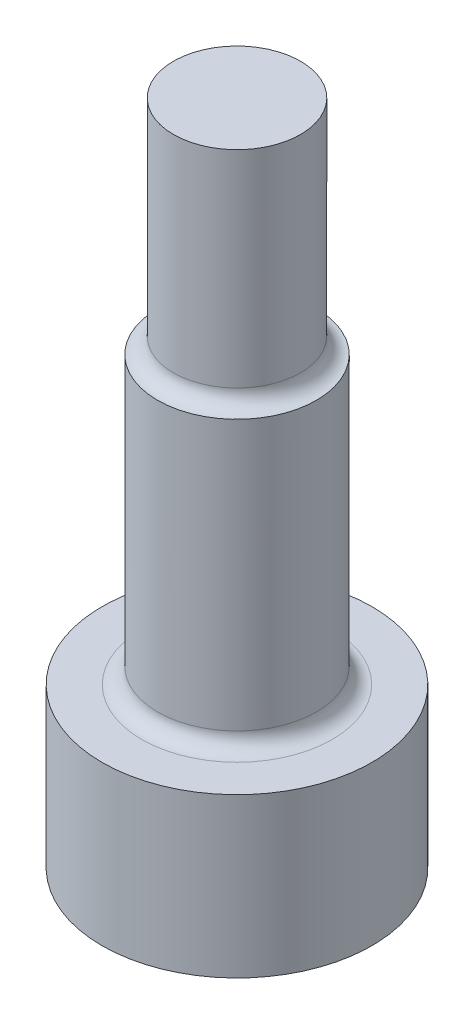
SolidWorks part; units mm, degrees
material "Chrome Stainless Steel"
ref_plane "Front Plane" through (0, 0, 0) normal (0, 0, 1) x (1, 0, 0)
ref_plane "Top Plane" through (0, 0, 0) normal (0, 1, 0) x (1, 0, 0)
ref_plane "Right Plane" through (0, 0, 0) normal (1, 0, 0) x (0, 0, -1)
sketch "Sketch1" plane through (0, 0, 0) normal (0, 0, 1) x (1, 0, 0)
  line L0 (0, 0) -> (4.25, 0)
  line L1 (4.675, 0) -> (-4.675, 0) construction
  line L2 (4.25, 0) -> (4.25, 5)
  line L3 (4.25, 5) -> (2.5, 5)
  line L4 (2.5, 5) -> (2.5, 14)
  line L5 (2.5, 14) -> (2, 14)
  line L6 (0, -4.675) -> (0, 4.675) construction
  line L7 (0, 21) -> (0, 0)
  line L8 (2, 14) -> (2, 21)
  line L9 (2, 21) -> (0, 21)
  dimension "D1" = 5
  dimension "D2" = 4.25
  dimension "D3" = 2.5
  dimension "D4" = 2
  dimension "D5" = 16
  dimension "D6" = 7
revolve "Revolve1" add sketch "Sketch1" angle 360 about L7
sketch "Sketch2" plane through (0, 0, 0) normal (0, -1, 0) x (1, 0, 0)
  line L1 (0, -1.7321) -> (1.5, -0.866)
  line L2 (1.5, -0.866) -> (1.5, 0.866)
  line L3 (1.5, 0.866) -> (0, 1.7321)
  line L4 (0, 1.7321) -> (-1.5, 0.866)
  line L5 (-1.5, 0.866) -> (-1.5, -0.866)
  line L6 (-1.5, -0.866) -> (0, -1.7321)
  circle A0 centre (0, 0) radius 1.5 construction
  dimension "D1" = 3
extrude "Cut-Extrude1" cut sketch "Sketch2" against normal blind 2
fillet "Fillet1" radius 0.5 1 edges at (0, 5, 2.5)
fillet "Fillet2" radius 0.5 1 edges at (0, 14, 2)
